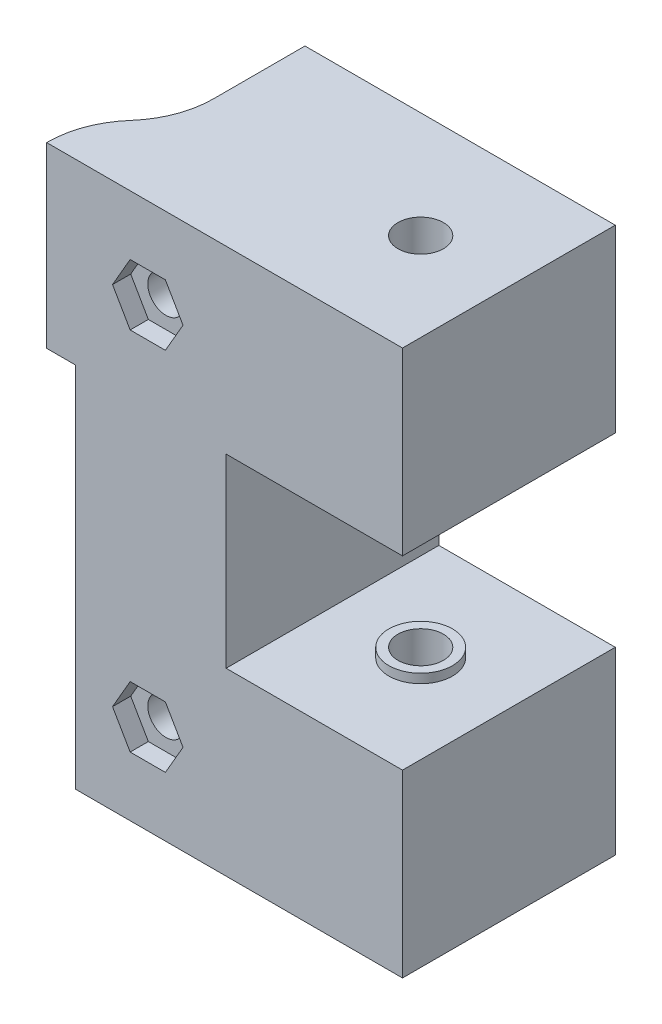
SolidWorks part; units mm, degrees
ref_plane "Front Plane" through (0, 0, 0) normal (0, 0, 1) x (1, 0, 0)
ref_plane "Top Plane" through (0, 0, 0) normal (0, 1, 0) x (1, 0, 0)
ref_plane "Right Plane" through (0, 0, 0) normal (1, 0, 0) x (0, 0, -1)
sketch "MainBlock" plane through (0, 0, 0) normal (0, 0, 1) x (1, 0, 0)
  line L0 (0, 0) -> (39.125, 0)
  line L1 (39.125, 0) -> (39.125, 19.8)
  line L2 (39.125, 19.8) -> (19.725, 19.8)
  line L3 (19.725, 19.8) -> (19.725, 40.2)
  line L4 (19.725, 40.2) -> (39.125, 40.2)
  line L5 (39.125, 40.2) -> (39.125, 60)
  line L6 (39.125, 60) -> (0, 60)
  line L7 (0, 60) -> (0, 0)
  circle A0 centre (11.1125, 50.1) radius 2
  circle A1 centre (11.1125, 9.9) radius 2
  dimension "D4" = 4
  dimension "D1" = 39.125
  dimension "D2" = 60
  dimension "D3" = 20.4
  dimension "D5" = 19.4
  dimension "D6" = 11.1125
  dimension "D7" = 9.9
  dimension "D8" = 9.9
extrude "MainBlockBoss-Extrude1" add sketch "MainBlock" along normal blind 23.4
sketch "TopHoleCut-Sketch2" plane through (0, 60, 0) normal (0, 1, 0) x (1, 0, 0)
  line L0 (39.125, 0) -> (0, 0) construction
  circle A0 centre (29.425, -11.7) radius 2.5
  dimension "D3" = 5
  dimension "D1" = 11.7
  dimension "D2" = 9.7
extrude "TopHoleCut-Extrude1" cut sketch "TopHoleCut-Sketch2" against normal blind 45
sketch "MountHoleBoreSketch3" plane through (0, 0, 23.4) normal (0, 0, 1) x (1, 0, 0)
  line L1 (14.9875, 50.1) -> (13.05, 53.4558)
  line L2 (13.05, 53.4558) -> (9.175, 53.4558)
  line L3 (9.175, 53.4558) -> (7.2375, 50.1)
  line L4 (7.2375, 50.1) -> (9.175, 46.7442)
  line L5 (9.175, 46.7442) -> (13.05, 46.7442)
  line L6 (13.05, 46.7442) -> (14.9875, 50.1)
  line L7 (14.9875, 9.9) -> (13.05, 13.2558)
  line L8 (13.05, 13.2558) -> (9.175, 13.2558)
  line L9 (9.175, 13.2558) -> (7.2375, 9.9)
  line L10 (7.2375, 9.9) -> (9.175, 6.5442)
  line L11 (9.175, 6.5442) -> (13.05, 6.5442)
  line L12 (13.05, 6.5442) -> (14.9875, 9.9)
  circle A0 centre (11.1125, 50.1) radius 3.3558 construction
  circle A1 centre (11.1125, 9.9) radius 3.3558 construction
  point P10 (11.1125, 53.4558)
  dimension "D1" = 7.75
extrude "MountHoleBoreCut-Extrude2" cut sketch "MountHoleBoreSketch3" against normal blind 2
sketch "TopSpacerSketch4" plane through (0, 40.2, 0) normal (0, -1, 0) x (1, 0, 0)
  circle A0 centre (29.425, 11.7) radius 3.5
  circle A1 centre (29.425, 11.7) radius 2.5
  circle A2 centre (29.425, 11.7) radius 2.5 construction
  dimension "D1" = 7
extrude "TopSpacerBoss-Extrude2" add sketch "TopSpacerSketch4" along normal blind 1
sketch "LowerSpacerSketch5" plane through (0, 19.8, 0) normal (0, 1, 0) x (1, 0, 0)
  circle A0 centre (29.425, -11.7) radius 2.5
  circle A1 centre (29.425, -11.7) radius 2.5 construction
  circle A2 centre (29.425, -11.7) radius 3.5
  circle A3 centre (29.425, -11.7) radius 3.5 construction
extrude "LowerSpacerBoss-Extrude3" add sketch "LowerSpacerSketch5" along normal blind 1
sketch "PushPinHoleSketch1" plane through (0, 0, 0) normal (0, -1, 0) x (1, 0, 0)
  circle A0 centre (29.425, 11.7) radius 1
  circle A1 centre (29.425, 11.7) radius 2.5 construction
  dimension "D1" = 2
extrude "PushPinHoleCut-Extrude1" cut sketch "PushPinHoleSketch1" against normal through all
sketch "ScrewCollisionSketch2" plane through (0, 0, 0) normal (-1, 0, 0) x (0, 0, 1)
  line L0 (0, 60) -> (0, 0) construction
  line L1 (0, 60) -> (18.72, 60)
  line L2 (0, 60) -> (0, 0)
  line L3 (0, 0) -> (18.72, 0)
  line L4 (18.72, 60) -> (18.72, 0)
  line L5 (23.4, 0) -> (0, 0) construction
  dimension "D1" = 18.72
extrude "ScrewCollisionCut-Extrude2" cut sketch "ScrewCollisionSketch2" against normal blind 5
fillet "ScrewCollisionFillet1" radius 10 1 edges at (5, 30, 18.72)
fillet "ScrewCollisionFillet2" radius 10 1 edges at (0, 30, 18.72)
sketch "MidRailIndentSketch1" plane through (0, 0, 23.4) normal (0, 0, 1) x (1, 0, 0)
  line L0 (0, 60) -> (0, 0) construction
  line L1 (0, 40.4) -> (3.175, 40.4)
  line L2 (0, 40.4) -> (0, 0)
  line L3 (0, 0) -> (3.175, 0)
  line L4 (3.175, 40.4) -> (3.175, 0)
  line L5 (39.125, 60) -> (0, 60) construction
  line L6 (0, 0) -> (39.125, 0) construction
  dimension "D1" = 19.6
  dimension "D3" = 3.175
extrude "MidRailIndentCut-Extrude1" cut sketch "MidRailIndentSketch1" against normal through all
equation "\"BeltTensionerWidth\"= \"MidRailToAlignWithGantryBlock\" + \"BeltTensionerInnerWidth\" / 2 + \"RailThickness\""
equation "\"BeltTensionerHeight\"= 60mm"
equation "\"BeltTensionerDepth\"= \"BeltTensionerBackWallThickness\" + \"BeltTensionerInnerDepth\"'Equals 23.4"
equation "\"BeltTensionerInnerWidth\"= \"20TGT2PulleyDiameter\" + \"BeltTensionerSpaceBetweenPulleyAndWall\""
equation "\"BeltTensionerInnerHeight\"= \"20TGT2PulleyWidth\" * 2 + \"1mmSpacer\" * 3"
equation "\"BeltTensionerBackWallThickness\"= 4mm"
equation "\"BeltTensionerInnerDepth\"= \"20TGT2PulleyDiameter\" + \"BeltTensionerSpaceBetweenPulleyAndWall\""
equation "\"RailThickness\"= .125in'Spec"
equation "\"HoleOffsetFromEdge\"= \"RailThickness\" * 2.5"
equation "\"LinearGBWithRailDepth\"= 12.75mm'Spec"
equation "\"GABDistanceFromBackToFirstPulley\"= 13.5mm"
equation "\"MidRailToAlignWithGantryBlock\"= \"LinearGBWithRailDepth\" + \"GABDistanceFromBackToFirstPulley\"'All outside cogs must align"
equation "\"20TGT2PulleyDiameter\"= 17.9mm'Spec"
equation "\"BeltTensionerSpaceBetweenPulleyAndWall\"= 1.5mm"
equation "\"BeltTensionerMountingHoleDiameter\"= 4.0mm"
equation "\"BeltTensionerMountingHoleOffsetFromTopOrBottom\"= ( \"BeltTensionerHeight\" - \"BeltTensionerInnerHeight\" ) / 4"
equation "\"20TGT2PulleyWidth\"= 8.7mm'The STL of the Pulley in the diagram is a bit larger"
equation "\"1mmSpacer\"= 1mm"
equation "\"SteelShaft5mmHoleDiameter\"= 5mm"
equation "\"BeltTensionerMountingHoleOuterBoreDepth\"= 2mm"
equation "\"BeltTensionerMountingHoleOuterBoreDiameter\"= 7.75mm"
equation "\"7mmx1mmSpacerDiameter\"= 7mm"
equation "\"7mmx1mmSpacerHeight\"= 1mm"
equation "\"D1@MainBlock\" = \"BeltTensionerWidth\""
equation "\"D2@MainBlock\" = \"BeltTensionerHeight\""
equation "\"D3@MainBlock\" = \"BeltTensionerInnerHeight\""
equation "\"D4@MainBlock\" = \"BeltTensionerMountingHoleDiameter\""
equation "\"D5@MainBlock\" = \"BeltTensionerInnerWidth\""
equation "\"D6@MainBlock\"=\"HoleOffsetFromEdge\" + \"RailThickness\""
equation "\"D7@MainBlock\"=\"BeltTensionerMountingHoleOffsetFromTopOrBottom\""
equation "\"D8@MainBlock\"=\"BeltTensionerMountingHoleOffsetFromTopOrBottom\""
equation "\"D1@MainBlockBoss-Extrude1\" = \"BeltTensionerDepth\""
equation "\"D1@TopHoleCut-Sketch2\" = \"BeltTensionerDepth\" / 2"
equation "\"D3@TopHoleCut-Sketch2\" = \"SteelShaft5mmHoleDiameter\""
equation "\"D1@MountHoleBoreSketch3\" = \"BeltTensionerMountingHoleOuterBoreDiameter\""
equation "\"D1@MountHoleBoreCut-Extrude2\"=\"BeltTensionerMountingHoleOuterBoreDepth\""
equation "\"D1@TopSpacerSketch4\" = \"7mmx1mmSpacerDiameter\""
equation "\"D1@TopSpacerBoss-Extrude2\" = \"7mmx1mmSpacerHeight\""
equation "\"D1@LowerSpacerBoss-Extrude3\" = \"7mmx1mmSpacerHeight\""
equation "\"SteelPinPushHoleDiameter\"= 2mm"
equation "\"D1@PushPinHoleSketch1\" = \"SteelPinPushHoleDiameter\""
equation "\"BeltTensionerSteelShaftHoleDepthFromTop\"= ( \"SteelShaftLength\" - \"BeltTensionerInnerHeight\" ) / 2 + ( \"BeltTensionerHeight\" - \"BeltTensionerInnerHeight\" ) / 2 + \"BeltTensionerInnerHeight\"'Equals 45"
equation "\"SteelShaftLength\"= 30mm"
equation "\"D1@TopHoleCut-Extrude1\"=\"BeltTensionerSteelShaftHoleDepthFromTop\""
equation "\"D2@TopHoleCut-Sketch2\"=\"BeltTensionerWidth\" -\"MidRailToAlignWithGantryBlock\" - \"RailThickness\""
equation "\"D1@ScrewCollisionSketch2\" = \"BeltTensionerDepth\" * .8"
equation "\"D3@MidRailIndentSketch1\" = \"RailThickness\""
equation "\"MidLeftOrRightSideRailHeight\"= 2.0in"
equation "\"D1@MidRailIndentSketch1\"=\"DistanceAboveMidSideRailToBeltTensioner\""
equation "\"LinearRailWidth\"= 12mm'Spec"
equation "\"MidSideRailVerticalOffset\"= \"LinearRailWidth\" + 3mm'Allows space for RodStabilizer to attach to bottom of MidSideRail"
equation "\"DistanceAboveMidSideRailToBeltTensioner\"= \"MidSideRailVerticalOffset\" + \"BeltTensionerHeight\" / 2 - \"MidLeftOrRightSideRailHeight\" / 2"
